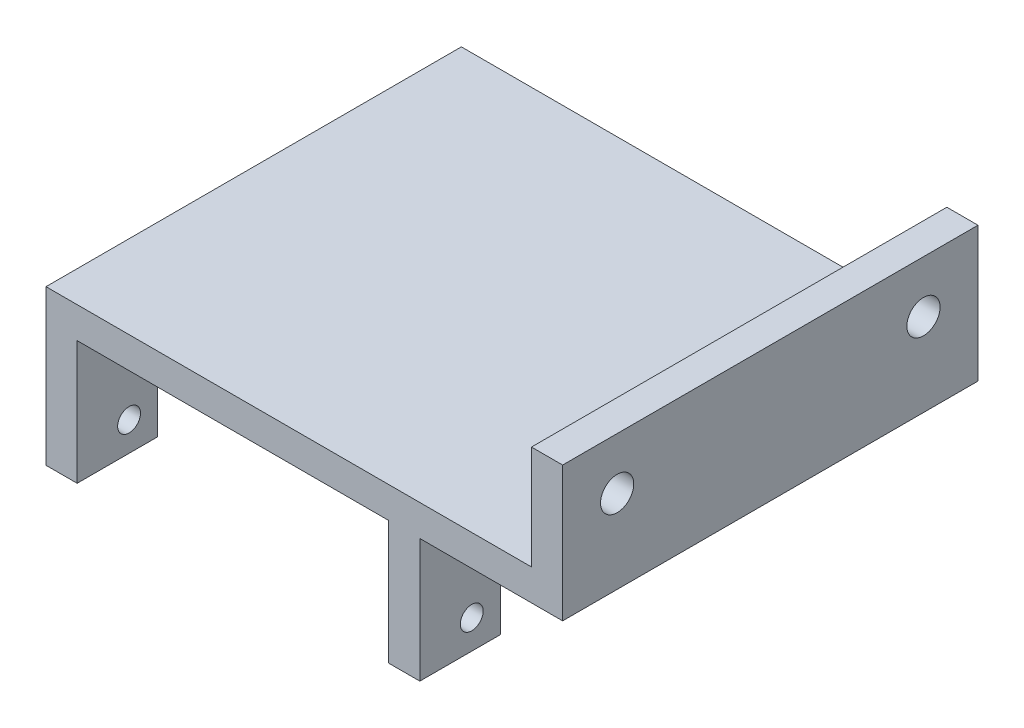
SolidWorks part; units mm, degrees
ref_plane "Front Plane" through (0, 0, 0) normal (0, 0, 1) x (1, 0, 0)
ref_plane "Top Plane" through (0, 0, 0) normal (0, 1, 0) x (1, 0, 0)
ref_plane "Right Plane" through (0, 0, 0) normal (1, 0, 0) x (0, 0, -1)
sketch "Sketch2" plane through (0, 0, 0) normal (0, 1, 0) x (1, 0, 0)
  line L1 (24.875, 20) -> (-24.875, 20)
  line L2 (24.875, 20) -> (24.875, -20)
  line L3 (24.875, -20) -> (-24.875, -20)
  line L4 (-24.875, 20) -> (-24.875, -20)
  line L5 (24.875, 20) -> (-24.875, -20) construction
  line L6 (24.875, -20) -> (-24.875, 20) construction
  line L7 (-24.875, 20) -> (-21.875, 20)
  line L8 (-24.875, 20) -> (-24.875, -20)
  line L9 (-24.875, -20) -> (-21.875, -20)
  line L10 (-21.875, 20) -> (-21.875, -20)
  line L11 (8.125, 20) -> (11.125, 20)
  line L12 (8.125, 20) -> (8.125, -20)
  line L13 (8.125, -20) -> (11.125, -20)
  line L14 (11.125, 20) -> (11.125, -20)
  line L15 (21.875, 20) -> (24.875, 20)
  line L16 (21.875, 20) -> (21.875, -20)
  line L17 (21.875, -20) -> (24.875, -20)
  line L18 (24.875, 20) -> (24.875, -20)
  point P0 (0, 0)
  dimension "D1" = 3
  dimension "D2" = 16.75
  dimension "D3" = 30
  dimension "D4" = 40
extrude "Boss-Extrude1" add sketch "Sketch2" along normal blind 3 contours L2 L3 L4 L1
extrude "Boss-Extrude3" add sketch "Sketch2<4>" against normal blind 11.9 contours L14 L1 L12 L3 | L10 L1 L4 L3 region at (9.625, 0, 0) region at (-23.375, 0, 0)
sketch "Sketch2<4>" plane through (0, 0, 0) normal (0, 1, 0) x (1, 0, 0) same geometry as "Sketch2"
extrude "Boss-Extrude4" add sketch "Sketch2<5>" along normal blind 13 contours L1 L16 L3 L2 region at (23.375, 0, 0)
sketch "Sketch2<5>" plane through (0, 0, 0) normal (0, 1, 0) x (1, 0, 0) same geometry as "Sketch2"
sketch "Sketch3" plane through (-24.875, 0, 0) normal (-1, 0, 0) x (0, 0, 1)
  line L0 (27.3625, 0) -> (-27.3625, 0) construction
  line L6 (-20, -11.9) -> (20, -11.9) construction
  line L11 (-12.25, -11.9) -> (12.25, -11.9)
  line L12 (-12.25, -11.9) -> (-12.25, -5.5)
  line L13 (-12.25, -5.5) -> (12.25, -5.5)
  line L14 (12.25, -11.9) -> (12.25, -5.5)
  circle A0 centre (-8.5, -2.8) radius 1.1
  circle A1 centre (-15, -9.1) radius 1.1
  point P13 (0, -5.5)
  dimension "D1" = 2.2
  dimension "D2" = 2.8
  dimension "D3" = 8.5
  dimension "D4" = 6.5
  dimension "D5" = 6.3
  dimension "D6" = 5.5
  dimension "D7" = 24.5
extrude "Cut-Extrude1" cut sketch "Sketch3" against normal up to surface (36 mm away) up to face at (11.125, -5.95, 0)
sketch "Sketch4" plane through (21.875, 0, 0) normal (-1, 0, 0) x (0, 0, 1)
  line L1 (20, 3) -> (-20, 3) construction
  circle A0 centre (-14.75, 8) radius 1.6
  dimension "D1" = 3.2
  dimension "D2" = 5
  dimension "D3" = 14.75
extrude "Cut-Extrude2" cut sketch "Sketch4" against normal up to surface (3 mm away) up to face at (24.875, 6.5, 0)
mirror "Mirror2" about plane through (0, 0, 0) normal (0, 0, 1) of "Cut-Extrude1", "Cut-Extrude2"
move or copy body "Body-Move/Copy1" [suppressed] bodies to move or copy 108
